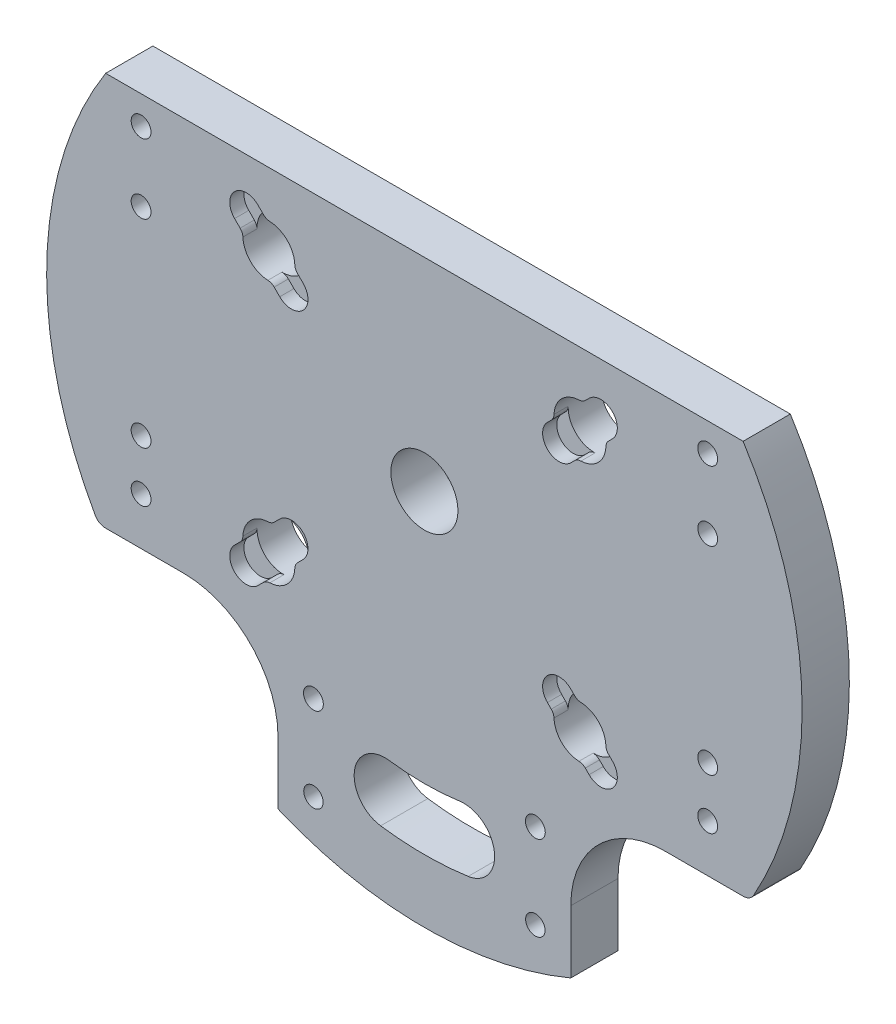
SolidWorks part; units mm, degrees
ref_plane "Front Plane" through (0, 0, 0) normal (0, 0, 1) x (1, 0, 0)
ref_plane "Top Plane" through (0, 0, 0) normal (0, 1, 0) x (1, 0, 0)
ref_plane "Right Plane" through (0, 0, 0) normal (1, 0, 0) x (0, 0, -1)
other "Configuration Table"
sketch "草图5" plane through (0, 0, 0) normal (0, 0, 1) x (1, 0, 0)
  line L0 (0, 0) -> (0, 43.4) construction
  line L1 (-67.5, 42.9389) -> (67.5, 42.9389)
  arc A0 (-67.5, 42.9389) -> (67.5, 42.9389) centre (0, 0) ccw
extrude "凸台-拉伸2" add sketch "草图5" along normal blind 10
sketch "草图6" plane through (0, 0, 0) normal (0, 0, -1) x (-1, 0, 0)
  line L0 (0, 0) -> (0, 62) construction
  line L1 (0, 0) -> (-51.9615, -30) construction
  line L2 (0, 0) -> (-80, 0) construction
  circle A0 centre (0, 0) radius 80 construction
  circle A1 centre (-51.9615, 30) radius 2.5
  circle A2 centre (-51.9615, -30) radius 2.5
  circle A3 centre (51.9615, -30) radius 2.5
  circle A4 centre (51.9615, 30) radius 2.5
  point P13 (0, 0)
  dimension "D2" = 2
  dimension "D1" = 60
extrude "切除-拉伸1" cut sketch "草图6" against normal blind 8
sketch "草图7" plane through (0, 0, 0) normal (0, 0, -1) x (-1, 0, 0)
  circle A0 centre (32.9399, -27.6399) radius 5.5
  circle A1 centre (32.9399, 27.6399) radius 5.5
  circle A2 centre (-32.9465, 27.632) radius 5.5
  circle A3 centre (-32.9465, -27.632) radius 5.5
extrude "切除-拉伸2" cut sketch "草图7" against normal through all
sketch "草图8" plane through (0, 0, 10) normal (0, 0, 1) x (1, 0, 0)
  line L0 (0, 0) -> (0, -56.1) construction
  line L1 (0, 0) -> (-9.2723, -65.9759) construction
  line L2 (0, 0) -> (9.2723, -65.9759) construction
  arc A0 (-9.2723, -65.9759) -> (9.2723, -65.9759) centre (0, 0) ccw
  arc A1 (-7.4597, -53.0784) -> (7.4597, -53.0784) centre (0, 0) ccw
  arc A2 (-9.2723, -65.9759) -> (-7.4597, -53.0784) centre (-8.366, -59.5271) cw
  arc A3 (9.2723, -65.9759) -> (7.4597, -53.0784) centre (8.366, -59.5271) ccw
  dimension "D1" = 8
  dimension "D2" = 8
extrude "切除-拉伸3" cut sketch "草图8" against normal through all
sketch "草图9" plane through (0, 0, 10) normal (0, 0, 1) x (1, 0, 0)
  line L0 (-32.9399, 27.6399) -> (-32.9399, 22.1399) construction
  line L1 (0, 0) -> (80, 0) construction
  line L2 (-37.721, 32.4209) -> (-28.1588, 22.8588) construction
  line L3 (-35.2461, 34.8958) -> (-25.684, 25.3337)
  line L4 (-40.1959, 29.9461) -> (-30.6337, 20.3839)
  line L5 (32.9465, 27.632) -> (32.9465, 22.132) construction
  line L6 (37.3573, 32.0428) -> (28.5357, 23.2212) construction
  line L7 (39.8322, 29.5679) -> (31.0106, 20.7463)
  line L8 (34.8824, 34.5177) -> (26.0608, 25.6961)
  line L9 (-37.721, -32.4209) -> (-28.1588, -22.8588) construction
  line L10 (-35.2461, -34.8958) -> (-25.684, -25.3337)
  line L11 (-40.1959, -29.9461) -> (-30.6337, -20.3839)
  line L12 (37.3573, -32.0428) -> (28.5357, -23.2212) construction
  line L13 (39.8322, -29.5679) -> (31.0106, -20.7463)
  line L14 (34.8824, -34.5177) -> (26.0608, -25.6961)
  circle A0 centre (-32.9399, 27.6399) radius 5.5 construction
  arc A1 (-67.5, 42.9389) -> (67.5, 42.9389) centre (0, 0) ccw construction
  arc A2 (-35.2461, 34.8958) -> (-40.1959, 29.9461) centre (-37.721, 32.4209) ccw
  arc A3 (-30.6337, 20.3839) -> (-25.684, 25.3337) centre (-28.1588, 22.8588) ccw
  circle A4 centre (32.9465, 27.632) radius 5.5 construction
  arc A5 (39.8322, 29.5679) -> (34.8824, 34.5177) centre (37.3573, 32.0428) ccw
  arc A6 (26.0608, 25.6961) -> (31.0106, 20.7463) centre (28.5357, 23.2212) ccw
  arc A7 (-35.2461, -34.8958) -> (-40.1959, -29.9461) centre (-37.721, -32.4209) cw
  arc A8 (-30.6337, -20.3839) -> (-25.684, -25.3337) centre (-28.1588, -22.8588) cw
  arc A9 (39.8322, -29.5679) -> (34.8824, -34.5177) centre (37.3573, -32.0428) cw
  arc A10 (26.0608, -25.6961) -> (31.0106, -20.7463) centre (28.5357, -23.2212) cw
  point P14 (-32.9399, 27.6399)
  point P26 (32.9465, 27.632)
  point P33 (-32.9399, -27.6399)
  point P40 (32.9465, -27.632)
  dimension "D2" = 45
  dimension "D1" = 45
extrude "切除-拉伸4" cut sketch "草图9" against normal blind 3
fillet "圆角1" radius 2 16 edges at (-33.465, -33.1147, 8.5) (-27.465, -27.1147, 8.5) (-38.4148, -28.165, 8.5) (-32.4148, -22.165, 8.5) (33.4716, -33.1069, 8.5) (27.4716, -27.1069, 8.5) (38.4214, -28.1571, 8.5) (32.4214, -22.1571, 8.5) (27.4716, 27.1069, 8.5) (33.4716, 33.1069, 8.5) (-32.4148, 22.165, 8.5) (-27.465, 27.1147, 8.5) (-38.4148, 28.165, 8.5) (-33.465, 33.1147, 8.5) (32.4214, 22.1571, 8.5) (38.4214, 28.1571, 8.5)
sketch "草图13" plane through (0, 0, 10) normal (0, 0, 1) x (1, 0, 0)
  line L0 (-64.2082, -40.5) -> (-68.9909, -40.5)
  line L2 (-64.2082, -40.5) -> (-31, -40.5)
  line L3 (-31, -40.5) -> (-31, -73.7496)
  line L4 (-31, -73.7496) -> (31, -73.7496)
  line L5 (31, -73.7496) -> (31, -40.5)
  line L6 (31, -40.5) -> (68.9909, -40.5)
  arc A0 (-67.5, 42.9389) -> (67.5, 42.9389) centre (0, 0) ccw construction
  arc A2 (-68.9909, -40.5) -> (68.9909, -40.5) centre (0, 0) ccw
extrude "切除-拉伸7" cut sketch "草图13" against normal through all contours L0 A2 L3 L2 | L5 A2 L6 region at (-44.9947, -52.8, 10) region at (44.9947, -52.8, 10)
sketch "草图16" plane through (0, 0, 0) normal (0, 0, -1) x (-1, 0, 0)
  line L0 (60, 42.9389) -> (60, -40.4611) construction
  line L1 (52.5, 42.9389) -> (67.5, 42.9389) construction
  line L2 (67.5, -40.4611) -> (59.7, -40.4611) construction
  line L4 (52.5, 16.2389) -> (67.5, 16.2389) construction
  line L5 (52.5, -13.7611) -> (67.5, -13.7611) construction
  circle A0 centre (60, 36.9389) radius 3.5
  circle A1 centre (60, 22.2389) radius 3.5
  circle A2 centre (60, -19.7611) radius 3.5
  circle A3 centre (60, -30.4611) radius 3.5
  dimension "D1" = 6
  dimension "D3" = 6
  dimension "D4" = 10
  dimension "D2" = 6
extrude "切除-拉伸8" cut sketch "草图16" against normal blind 3
sketch "草图18" plane through (0, 0, 0) normal (0, 0, -1) x (-1, 0, 0)
  circle A0 centre (60, -30.4611) radius 2.1
  circle A1 centre (60, -19.7611) radius 2.1
  circle A2 centre (60, 22.2389) radius 2.1
  circle A3 centre (60, 36.9389) radius 2.1
extrude "切除-拉伸9" cut sketch "草图18" against normal through all
mirror "镜向1" about plane through (0, 0, 0) normal (1, 0, 0) of "切除-拉伸8", "切除-拉伸9"
fillet "圆角2" radius 20 2 edges at (31, -40.5, 5) (-31, -40.5, 5)
fillet "圆角3" radius 2.5 2 edges at (68.9909, -40.5, 5) (-68.9909, -40.5, 5)
sketch "草图20" plane through (0, 0, 0) normal (0, 0, -1) x (-1, 0, 0)
  line L0 (31, -60.5) -> (31, -73.7496) construction
  circle A0 centre (23.5, -67.7496) radius 3.5
  circle A1 centre (23.5, -49.7496) radius 3.5
  dimension "D1" = 6
  dimension "D2" = 6
  dimension "D3" = 7.5
  dimension "D4" = 7.5
extrude "切除-拉伸11" cut sketch "草图20" against normal blind 3
sketch "草图21" plane through (0, 0, 0) normal (0, 0, -1) x (-1, 0, 0)
  line L0 (31, -60.5) -> (31, -73.7496) construction
  circle A1 centre (23.5, -49.7496) radius 2.1
  circle A2 centre (23.5, -67.7496) radius 2.0561
  dimension "D1" = 7.5
  dimension "D2" = 6
  dimension "D3" = 6
  dimension "D4" = 7.5
extrude "切除-拉伸12" cut sketch "草图21" against normal through all
mirror "镜向2" about plane through (0, 0, 0) normal (1, 0, 0) of "切除-拉伸12", "切除-拉伸11"
sketch "草图22" plane through (0, 0, 0) normal (0, 0, -1) x (-1, 0, 0)
  circle A0 centre (0, 0) radius 7.1
  dimension "D1" = 14.2
extrude "切除-拉伸13" cut sketch "草图22" against normal through all
chamfer "倒角1" [suppressed] distance 0.2 angle 45
chamfer "倒角2" [suppressed] distance 0.2 angle 45
